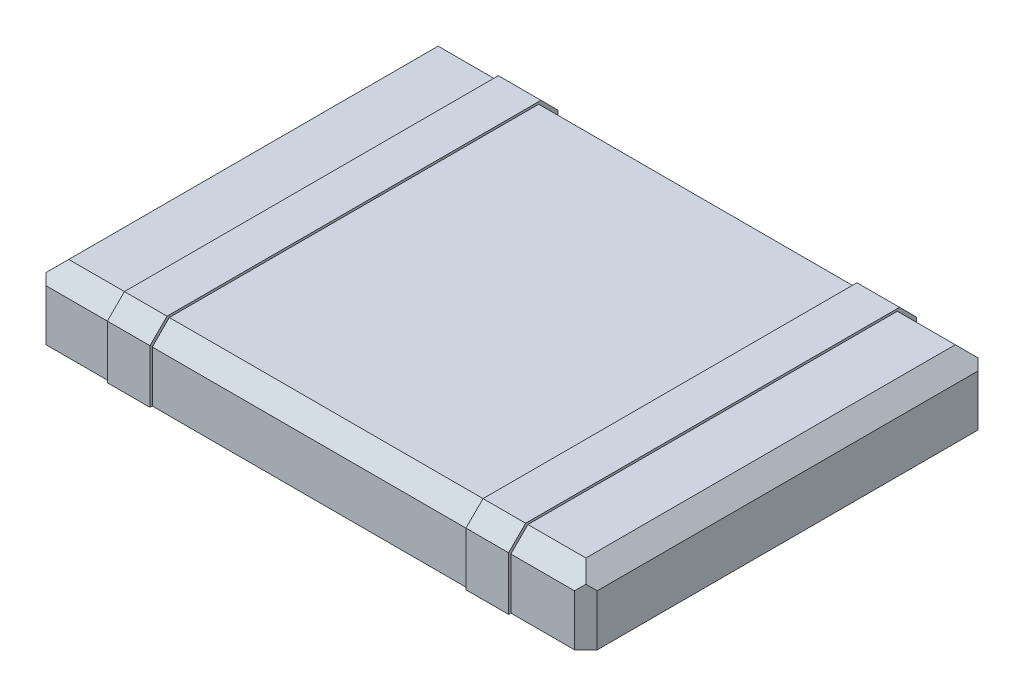
SolidWorks part; units mm, degrees
ref_plane "Alzado" through (0, 0, 0) normal (0, 0, 1) x (1, 0, 0)
ref_plane "Planta" through (0, 0, 0) normal (0, 1, 0) x (1, 0, 0)
ref_plane "Vista lateral" through (0, 0, 0) normal (1, 0, 0) x (0, 0, -1)
sketch "Croquis1" plane through (19.9205, 0, 21.3013) normal (0, 1, 0) x (1, 0, 0)
  line L6 (-44.1705, 39.0513) -> (4.3295, 39.0513)
  line L7 (-44.1705, 39.0513) -> (-44.1705, 3.5513)
  line L8 (-44.1705, 3.5513) -> (4.3295, 3.5513)
  line L9 (4.3295, 39.0513) -> (4.3295, 3.5513)
  line L10 (-44.1705, 39.0513) -> (4.3295, 3.5513) construction
  line L11 (-44.1705, 3.5513) -> (4.3295, 39.0513) construction
  point P0 (-19.9205, 21.3013)
  dimension "D1" = 35.5
  dimension "D2" = 48.5
extrude "Saliente-Extruir1" add sketch "Croquis1" along normal blind 6
sketch "Croquis2" plane through (0, 0, 0) normal (0, -1, 0) x (1, 0, 0)
  line L1 (-22.25, 16) -> (22.25, 16)
  line L2 (-22.25, 16) -> (-22.25, -16)
  line L3 (-22.25, -16) -> (22.25, -16)
  line L4 (22.25, 16) -> (22.25, -16)
  line L5 (-22.25, 16) -> (22.25, -16) construction
  line L6 (-22.25, -16) -> (22.25, 16) construction
  point P0 (0, 0)
  dimension "D1" = 32
  dimension "D2" = 44.5
chamfer "Chaflán1" distance 1 angle 45 4 edges at (-24.25, 3, 17.75) (-24.25, 3, -17.75) (24.25, 3, -17.75) (24.25, 3, 17.75)
sketch "Croquis3" plane through (0, 6, 0) normal (0, 1, 0) x (1, 0, 0)
  line L0 (17.65, 17.75) -> (17.65, -17.75)
  line L1 (23.25, 17.75) -> (-23.25, 17.75) construction
  line L2 (-23.25, -17.75) -> (23.25, -17.75) construction
  line L3 (17.65, -17.75) -> (13.9, -17.75)
  line L4 (13.9, -17.75) -> (13.9, 17.75)
  line L5 (13.9, 17.75) -> (17.65, 17.75)
  line L6 (24.25, -16.75) -> (24.25, 16.75) construction
  line L7 (0, 0) -> (0, 14.6557) construction
  line L8 (-13.9, 17.75) -> (-17.65, 17.75)
  line L9 (-17.65, 17.75) -> (-17.65, -17.75)
  line L10 (-13.9, -17.75) -> (-13.9, 17.75)
  line L11 (-17.65, -17.75) -> (-13.9, -17.75)
  dimension "D1" = 6.6
  dimension "D2" = 3.75
extrude "Saliente-Extruir3" add sketch "Croquis3" along normal blind 0.2
sketch "Croquis4" plane through (0, 0, 17.75) normal (0, 0, 1) x (1, 0, 0)
  line L0 (13.9, 6.2) -> (13.9, 0)
  line L2 (-23.25, 0) -> (23.25, 0) construction
  line L3 (13.9, 0) -> (17.65, 0)
  line L4 (17.65, 0) -> (17.65, 6.2)
  line L5 (17.65, 6.2) -> (13.9, 6.2)
  line L6 (0, 0) -> (0, 5.4904) construction
  line L7 (-17.65, 6.2) -> (-13.9, 6.2)
  line L8 (-17.65, 0) -> (-17.65, 6.2)
  line L9 (-13.9, 0) -> (-17.65, 0)
  line L10 (-13.9, 6.2) -> (-13.9, 0)
extrude "Saliente-Extruir4" add sketch "Croquis4" along normal blind 0.2
extrude "Cortar-Extruir1" cut sketch "Croquis2" against normal offset from surface (4 mm away) 2 up to face at (21.7167, 6, 0)
mirror "Simetría1" about plane through (0, 0, 0) normal (0, 0, 1) of "Saliente-Extruir4"
chamfer "Chaflán2" distance 1.5 angle 45 12 edges at (-15.775, 6.2, -17.95) (15.775, 6.2, -17.95) (-15.775, 6.2, 17.95) (15.775, 6.2, 17.95) (24.25, 6, 0) (20.45, 6, 17.75) (20.45, 6, -17.75) (0, 6, -17.75) (-20.45, 6, -17.75) (-24.25, 6, 0) (-20.45, 6, 17.75) (0, 6, 17.75)
sketch "Croquis5" plane through (0, 0, 0) normal (1, 0, 0) x (0, 0, -1)
  line L0 (17.95, 1.5026) -> (19.5882, -0.2379)
  line L1 (17.95, 0) -> (17.95, 4.7) construction
  line L2 (17.95, 1.5026) -> (17.95, -1.8156)
  arc A0 (17.95, -1.8156) -> (19.5882, -0.2379) centre (18.8878, -1.15) ccw
extrude "Saliente-Extruir5" add sketch "Croquis5" along normal mid plane 23
sketch "Croquis6" plane through (-11.5, 0, 0) normal (-1, 0, 0) x (0, 0, 1)
  circle A0 centre (-18.8878, -1.15) radius 0.5
  dimension "D1" = 1
extrude "Saliente-Extruir6" add sketch "Croquis6" along normal mid plane 2.3
mirror "Simetría2" about plane through (0, 0, 0) normal (1, 0, 0) of "Saliente-Extruir6"
